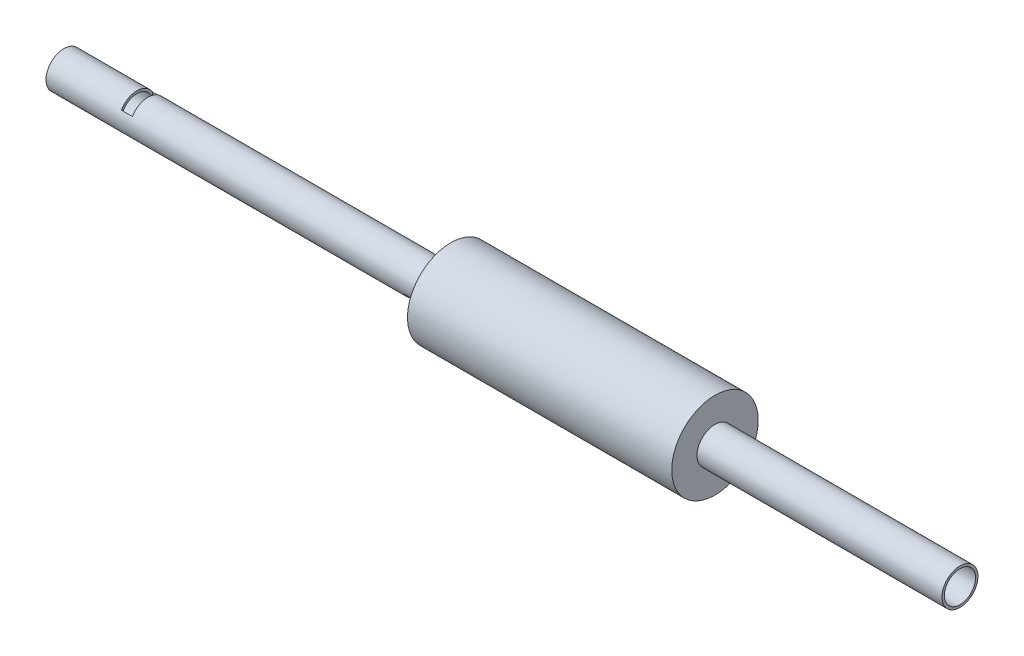
SolidWorks part; units mm, degrees
ref_plane "Front Plane" through (0, 0, 0) normal (0, 0, 1) x (1, 0, 0)
ref_plane "Top Plane" through (0, 0, 0) normal (0, 1, 0) x (1, 0, 0)
ref_plane "Right Plane" through (0, 0, 0) normal (1, 0, 0) x (0, 0, -1)
sketch "Sketch1" plane through (0, 0, 0) normal (0, 0, 1) x (1, 0, 0)
  line L0 (196.3562, 0) -> (-196.3562, 0) construction
  line L3 (157, 7.5) -> (-216, 7.5)
  line L4 (0, -42.6677) -> (0, 42.6677) construction
  line L7 (157, 7.5) -> (157, 0)
  line L8 (157, 0) -> (-157, 0) construction
  line L9 (-216, 7.5) -> (-216, 6.5)
  line L10 (-216, 6.5) -> (-157, 6.5)
  line L11 (-157, 6.5) -> (-157, 0) construction
  line L12 (-55, 18) -> (55, 18)
  line L13 (-55, 18) -> (-55, 7.5)
  line L14 (55, 18) -> (55, 7.5)
  line L15 (-157, 6.5) -> (157, 6.5)
  point P3 (0, 18)
  point P10 (0, 0)
  dimension "D1" = 157
  dimension "D3" = 59
  dimension "D4" = 15
  dimension "D5" = 13
  dimension "D6" = 36
  dimension "D7" = 110
  dimension "D2" = 157
revolve "Revolve1" add sketch "Sketch1" angle 360 about L0 region at (-29.5, 7, 0) region at (0, 12.75, 0)
sketch "Sketch2" plane through (0, 0, 0) normal (0, 1, 0) x (1, 0, 0)
  line L0 (157, 0) -> (-157, 0) construction
  line L1 (-68, -6.5) -> (-60, -6.5)
  line L2 (-68, -6.5) -> (-68, 6.5)
  line L3 (-68, 6.5) -> (-60, 6.5)
  line L4 (-60, -6.5) -> (-60, 6.5)
  line L5 (-68, -6.5) -> (-60, 6.5) construction
  line L6 (-68, 6.5) -> (-60, -6.5) construction
  line L7 (196.3562, 0) -> (-196.3562, 0) construction
  line L8 (-185.6, -6.5) -> (-181, -6.5)
  line L9 (-185.6, -6.5) -> (-185.6, 6.5)
  line L10 (-185.6, 6.5) -> (-181, 6.5)
  line L11 (-181, -6.5) -> (-181, 6.5)
  line L12 (-185.6, -6.5) -> (-181, 6.5) construction
  line L13 (-185.6, 6.5) -> (-181, -6.5) construction
  point P0 (-64, 0)
  point P7 (-183.3, 0)
  dimension "D1" = 5
  dimension "D2" = 8
  dimension "D3" = 13
  dimension "D4" = 13
  dimension "D5" = 181
  dimension "D6" = 4.6
extrude "Cut-Extrude1" cut sketch "Sketch2" against normal up to next contours L1 L4 L3 L2 region at (-64, 0, 0)
extrude "Cut-Extrude2" cut sketch "Sketch2<3>" along normal up to next contours L8 L11 L10 L9 region at (-183.3, 0, 0)
sketch "Sketch2<3>" plane through (0, 0, 0) normal (0, 1, 0) x (1, 0, 0) same geometry as "Sketch2"
equation "\"D2@Sketch1\"=\"D1@Sketch1\""
